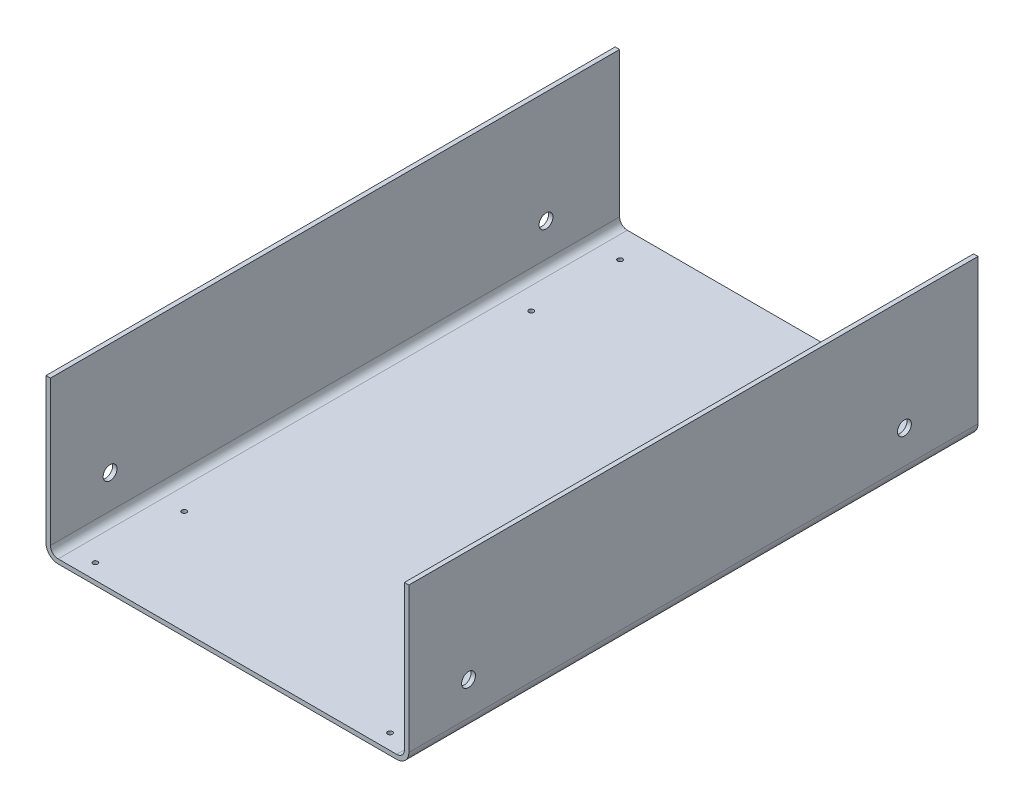
SolidWorks part; units mm, degrees
material "5052-H32"
ref_plane "Front Plane" through (0, 0, 0) normal (0, 0, 1) x (1, 0, 0)
ref_plane "Top Plane" through (0, 0, 0) normal (0, 1, 0) x (1, 0, 0)
ref_plane "Right Plane" through (0, 0, 0) normal (1, 0, 0) x (0, 0, -1)
sketch "Sketch1" plane through (0, 0, 0) normal (0, 0, 1) x (1, 0, 0)
  line L8 (127.5, 110) -> (127.5, 0)
  line L9 (-127.5, 0) -> (127.5, 0)
  line L10 (-127.5, 0) -> (-127.5, 110)
  line L11 (130.68, 110) -> (130.68, -3.18)
  line L12 (-130.68, -3.18) -> (130.68, -3.18)
  line L13 (-130.68, -3.18) -> (-130.68, 110)
  line L14 (127.5, 110) -> (130.68, 110)
  line L15 (-127.5, 110) -> (-130.68, 110)
  point P5 (0, 0)
  dimension "D2" = 110
  dimension "D4" = 110
  dimension "D3" = 255
  dimension "D1" = 3.18
extrude "Boss-Extrude1" add sketch "Sketch1" along normal blind 410
fillet "Inside Fillet" radius 5.5563 2 edges at (127.5, 0, 205) (-127.5, 0, 205)
fillet "Outside Fillet" radius 8.73 2 edges at (-130.68, -3.18, 205) (130.68, -3.18, 205)
sketch "Sketch2" plane through (130.68, 0, 0) normal (1, 0, 0) x (0, 0, -1)
  line L1 (-410, 5.55) -> (-410, 110) construction
  line L2 (0, 5.55) -> (0, 110) construction
  line L4 (-367, 29.5) -> (-367, 0) construction
  line L7 (-53, 29.5) -> (-53, 0) construction
  circle A0 centre (-367, 29.5) radius 5
  circle A1 centre (-53, 29.5) radius 5
  dimension "D3" = 10
  dimension "D4" = 10
  dimension "D1" = 43
  dimension "D2" = 29.5
  dimension "D5" = 53
  dimension "D6" = 29.5
extrude "Bearing Holes" cut sketch "Sketch2" against normal up to surface (261.36 mm away) up to face at (-130.68, 57.775, 205)
sketch "Sketch3" plane through (0, 0, 0) normal (0, 1, 0) x (1, 0, 0)
  line L0 (-106.15, -335) -> (-106.15, -399) construction
  line L1 (121.9437, -410) -> (-121.9438, -410) construction
  line L2 (-127.5, -410) -> (-127.5, 0) construction
  line L3 (-130.68, -205) -> (130.68, -205) construction
  line L4 (-130.68, -410) -> (-130.68, 0) construction
  line L5 (130.68, -410) -> (130.68, 0) construction
  line L6 (0, -410) -> (0, -205) construction
  line L7 (-106.15, -85) -> (-106.15, -21) construction
  line L8 (121.9437, 0) -> (-121.9438, 0) construction
  line L9 (106.15, -335) -> (106.15, -399) construction
  line L10 (106.15, -85) -> (106.15, -21) construction
  circle A0 centre (-106.15, -335) radius 1.7526
  circle A1 centre (-106.15, -399) radius 1.7526
  circle A6 centre (106.15, -399) radius 1.7526
  circle A7 centre (106.15, -335) radius 1.7526
  circle A8 centre (-106.15, -85) radius 1.7526
  circle A9 centre (-106.15, -21) radius 1.7526
  circle A10 centre (106.15, -21) radius 1.7526
  circle A11 centre (106.15, -85) radius 1.7526
  point P4 (-106.15, -367)
  point P23 (-106.15, -53)
  dimension "D4" = 3.5052
  dimension "D5" = 3.5052
  dimension "D6" = 3.5052
  dimension "D7" = 3.5052
  dimension "D1" = 64
  dimension "D2" = 43
  dimension "D3" = 21.35
  dimension "D8" = 64
  dimension "D9" = 21.35
  dimension "D10" = 53
extrude "Motor Mount Holes" cut sketch "Sketch3" against normal up to next
equation "\"W\"= 255mm"
equation "\"L\"= 410mm"
equation "\"Offset\"= 13mm"
equation "\"H\"= 110mm"
equation "\"Compartment Width\"= 80"
equation "\"T\"= 4.7625 * 2 / 3mm"
equation "\"Inside Fillet Radius\"= 5.55625mm"
equation "\"Hole\"=15mm"
equation "\"Wheel to Wall\"=43"
equation "\"D3@Sketch1\"=\"W\""
equation "\"D2@Sketch1\"=\"H\""
equation "\"D4@Sketch1\"=\"H\""
equation "\"D1@Boss-Extrude1\"=\"L\""
equation "\"D1@Inside Fillet\" = \"Inside Fillet Radius\""
equation "\"D1@Outside Fillet\" = \"Inside Fillet Radius\" + \"T\""
equation "\"D2@Sketch3\"=\"Wheel to Wall\""
